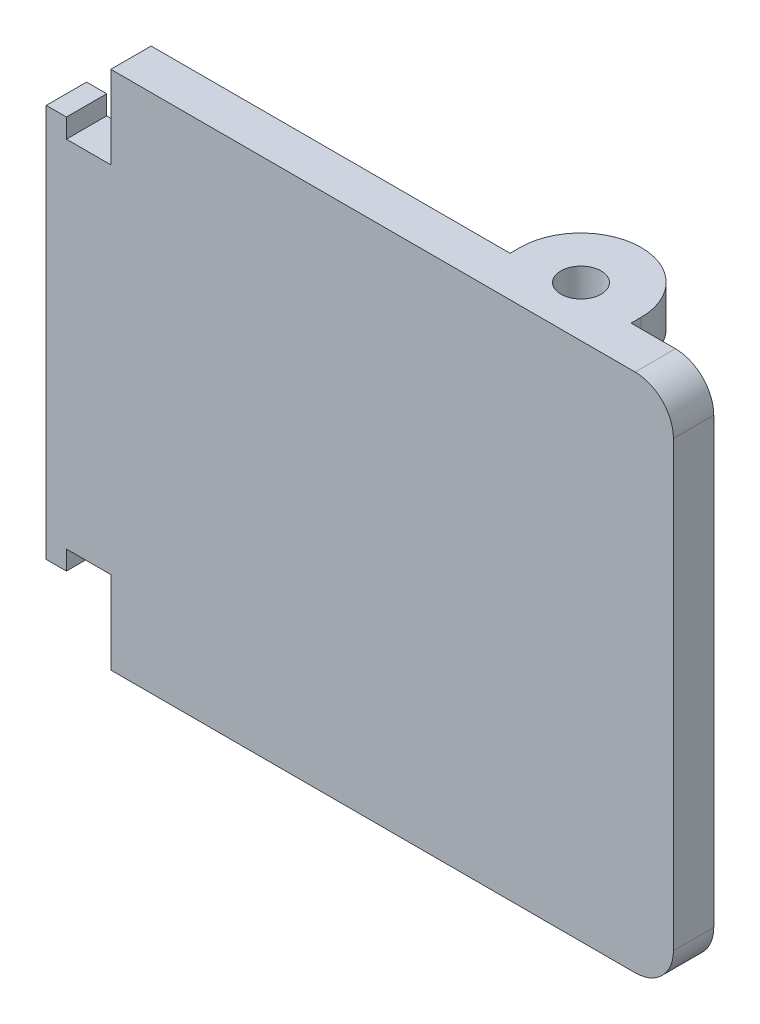
SolidWorks part; units mm, degrees
ref_plane "前视基准面" through (0, 0, 0) normal (0, 0, 1) x (1, 0, 0)
ref_plane "上视基准面" through (0, 0, 0) normal (0, 1, 0) x (1, 0, 0)
ref_plane "右视基准面" through (0, 0, 0) normal (1, 0, 0) x (0, 0, -1)
other "Configuration Table"
sketch "草图1" plane through (0, 0, 0) normal (0, 0, 1) x (1, 0, 0)
  line L0 (-14.1424, -0.7887) -> (-14.1424, 0.1613)
  line L1 (-14.1424, 0.1613) -> (-15.1424, 0.1613)
  line L2 (-15.1424, 0.1613) -> (-15.1424, -19.3387)
  line L3 (-11.9424, 3.3113) -> (-11.9424, -0.7887)
  line L4 (-11.9424, 6.4113) -> (-11.9424, -25.5887) construction
  line L5 (-11.9424, -0.7887) -> (-14.1424, -0.7887)
  line L6 (-11.9424, -22.4887) -> (14.0576, -22.4887)
  line L7 (15.9576, -20.5887) -> (15.9576, 1.4113)
  line L8 (14.0576, 3.3113) -> (-11.9424, 3.3113)
  line L9 (-11.9424, -22.4887) -> (14.0576, -22.4887)
  line L10 (15.9576, -20.5887) -> (15.9576, 1.4113)
  line L11 (14.0576, 3.3113) -> (-11.9424, 3.3113)
  line L13 (-14.1424, -18.3887) -> (-11.9424, -18.3887)
  line L14 (-11.9424, -22.4887) -> (-11.9424, -18.3887)
  line L15 (-14.1424, -18.3887) -> (-14.1424, -19.3387)
  line L16 (-14.1424, -19.3387) -> (-15.1424, -19.3387)
  arc A4 (14.0576, -22.4887) -> (15.9576, -20.5887) centre (14.0576, -20.5887) ccw
  arc A5 (15.9576, 1.4113) -> (14.0576, 3.3113) centre (14.0576, 1.4113) ccw
  arc A6 (14.0576, -22.4887) -> (15.9576, -20.5887) centre (14.0576, -20.5887) ccw
  arc A7 (15.9576, 1.4113) -> (14.0576, 3.3113) centre (14.0576, 1.4113) ccw
  point P6 (0, 0)
  point P11 (0, 0)
  point P14 (0, 0)
  point P15 (0, 0)
  point P17 (0, 0)
  point P19 (0, 0)
  point P25 (0, 0)
  point P26 (0, 0)
  point P27 (0, 0)
  point P28 (-14.1424, 0)
  point P29 (-15.1424, 0)
  point P30 (-19.4625, -19.4236)
  point P31 (-15.1424, -9.5887)
  point P32 (15.9576, -9.5887)
  dimension "D2" = 17.6
  dimension "D3" = 2.2
  dimension "D4" = 1
  dimension "D5" = 19.5
  dimension "D1" = 0.1
extrude "凸台-拉伸1" add sketch "草图1" against normal blind 2
sketch "草图2" plane through (0, 0, -2) normal (0, 0, -1) x (-1, 0, 0)
  line L0 (11.9424, -22.4887) -> (-14.0576, -22.4887) construction
  line L1 (-5.8576, -22.4887) -> (-11.8576, -22.4887)
  line L2 (-5.8576, -22.4887) -> (-5.8576, -20.4887)
  line L3 (-5.8576, -20.4887) -> (-11.8576, -20.4887)
  line L4 (-11.8576, -22.4887) -> (-11.8576, -20.4887)
  line L5 (-14.0576, 3.3113) -> (11.9424, 3.3113) construction
  line L6 (-5.8576, 3.3113) -> (-11.8576, 3.3113)
  line L7 (-5.8576, 3.3113) -> (-5.8576, 1.3113)
  line L8 (-5.8576, 1.3113) -> (-11.8576, 1.3113)
  line L9 (-11.8576, 3.3113) -> (-11.8576, 1.3113)
  line L10 (-18.0576, -20.5887) -> (-18.0576, 1.4113) construction
  dimension "D1" = 6
  dimension "D2" = 6.2
  dimension "D3" = 2
extrude "凸台-拉伸2" add sketch "草图2" along normal blind 3.5
fillet "圆角1" radius 3 4 edges at (11.8576, 2.3113, -5.5) (5.8576, 2.3113, -5.5) (11.8576, -21.4887, -5.5) (5.8576, -21.4887, -5.5)
sketch "草图3" plane through (0, -22.4887, 0) normal (0, -1, 0) x (1, 0, 0)
  circle A0 centre (8.8741, -2.5) radius 1
  dimension "D1" = 2
extrude "切除-拉伸1" cut sketch "草图3" against normal blind 5 draft 2
sketch "草图4" plane through (0, 3.3113, 0) normal (0, 1, 0) x (1, 0, 0)
  circle A0 centre (8.8741, 2.5) radius 1
  dimension "D1" = 2
extrude "切除-拉伸2" cut sketch "草图4" against normal blind 5 draft 2
